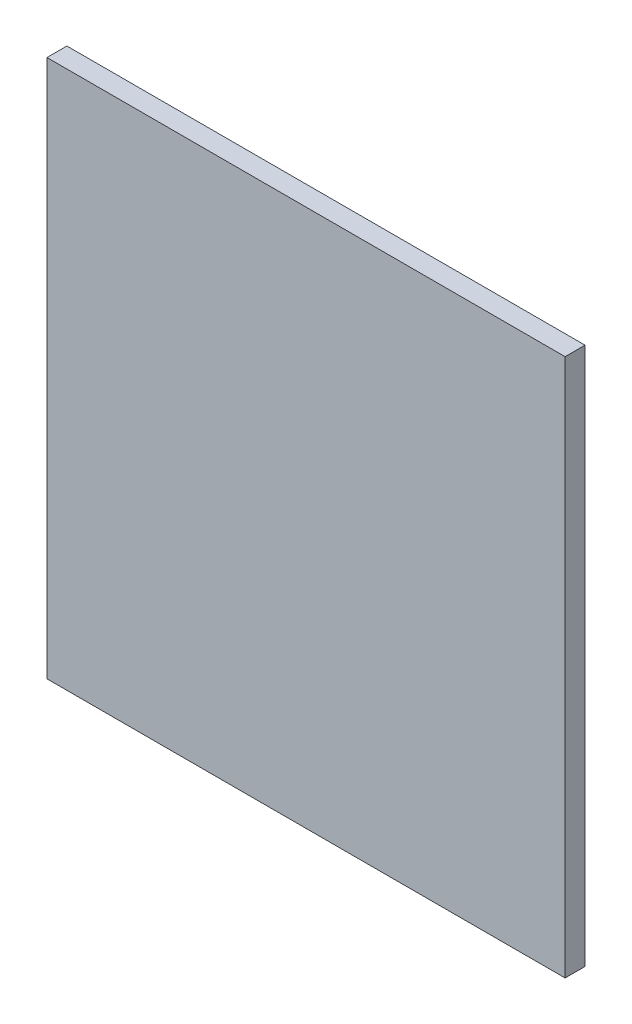
SolidWorks part; units mm, degrees
ref_plane "Front Plane" through (0, 0, 0) normal (0, 0, 1) x (1, 0, 0)
ref_plane "Top Plane" through (0, 0, 0) normal (0, 1, 0) x (1, 0, 0)
ref_plane "Right Plane" through (0, 0, 0) normal (1, 0, 0) x (0, 0, -1)
sketch "Sketch1" plane through (0, 0, 0) normal (0, 0, 1) x (1, 0, 0)
  line L0 (-6.35, 155.575) -> (-6.35, 130.175) construction
  line L1 (158.75, 155.575) -> (-6.35, 155.575)
  line L2 (158.75, 155.575) -> (158.75, -15.875)
  line L3 (158.75, -15.875) -> (-6.35, -15.875)
  line L4 (-6.35, 155.575) -> (-6.35, -15.875)
  line L6 (0, -15.875) -> (-6.35, -15.875) construction
extrude "Boss-Extrude1" add sketch "Sketch1" along normal blind 6.35
